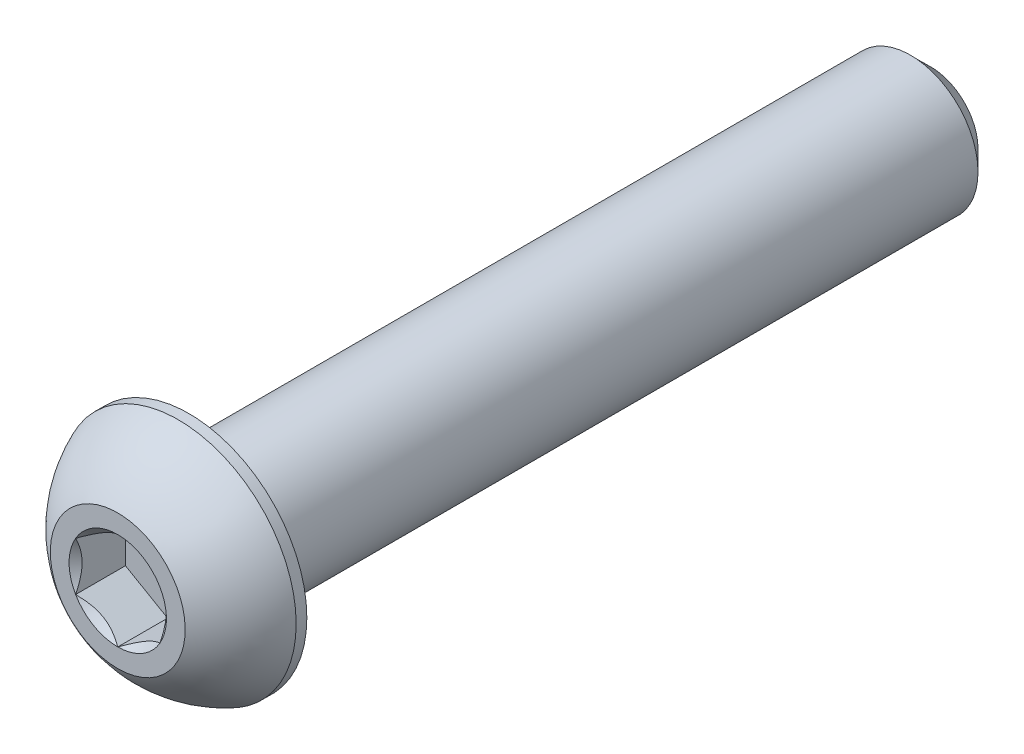
SolidWorks part; units mm, degrees
ref_plane "Front" through (0, 0, 0) normal (0, 0, 1) x (1, 0, 0)
ref_plane "Top" through (0, 0, 0) normal (0, 1, 0) x (1, 0, 0)
ref_plane "Right" through (0, 0, 0) normal (1, 0, 0) x (0, 0, -1)
sketch "Sketch1" plane through (0, 0, 0) normal (1, 0, 0) x (0, 0, -1)
  line L2 (3.3528, 3.175) -> (38.2778, 3.175)
  line L3 (38.2778, 3.175) -> (38.2778, 0)
  line L4 (38.2778, 0) -> (3.3528, 0)
  line L6 (2.8499, 5.5499) -> (3.3528, 5.5499) construction
  line L7 (38.2778, 3.175) -> (38.2778, -3.175) construction
  line L8 (0, 0) -> (3.3528, 0) construction
  line L9 (3.3528, 5.5499) -> (3.3528, -5.5499) construction
  line L11 (3.3528, 3.175) -> (3.3528, 0)
  line L13 (0, 1.9844) -> (0, -1.9844) construction
  line L14 (0, 1.9844) -> (0, 3.175) construction
  arc A3 (0, 3.175) -> (2.8499, 5.5499) centre (5.0603, 0) cw construction
  dimension "D1" = 0.5029
revolve "Revolve1" add sketch "Sketch1" angle 360 mid plane about L4
sketch "Sketch3" plane through (0, 0, -38.2778) normal (0, 0, -1) x (-1, 0, 0)
  circle A0 centre (0, 0) radius 3.175
curve "Helix/Spiral1" [suppressed] pitch 1.27 height 36.195 turns 28.5
sketch "Sketch2" plane through (0, 0, 0) normal (1, 0, 0) x (0, 0, -1)
  line L0 (38.2778, 3.175) -> (39.389, 3.175)
  line L1 (39.389, 3.175) -> (38.9128, 2.3501)
  line L2 (38.9128, 2.3501) -> (38.754, 2.3501)
  line L3 (38.754, 2.3501) -> (38.2778, 3.175)
  line L4 (38.5159, 2.7626) -> (39.1509, 2.7626) construction
  dimension "D1" = 60
  dimension "D2" = 0.1588
  dimension "D3" = 0.635
chamfer "Chamfer1" distance 0.9525 angle 45 1 edges at (0, 3.175, -38.2778)
sweep "Cut-Sweep1" [suppressed] cut profiles "Sketch2" path "Helix/Spiral1"
sketch "Sketch7" plane through (0, 0, 0) normal (1, 0, 0) x (0, 0, -1)
  line L6 (2.8499, 5.5499) -> (3.3528, 5.5499) construction
  line L8 (0, 0) -> (3.3528, 0) construction
  line L11 (3.3528, 5.5499) -> (3.3528, -5.5499) construction
  line L12 (2.8499, 5.5499) -> (3.3528, 5.5499)
  line L13 (0, 0) -> (3.3528, 0)
  line L14 (0, 1.9844) -> (0, -1.9844) construction
  line L15 (3.3528, 5.5499) -> (3.3528, 0)
  line L16 (0, 3.175) -> (0, 0)
  arc A2 (2.8499, 5.5499) -> (0, 3.175) centre (5.0603, 0) ccw construction
  arc A3 (2.8499, 5.5499) -> (0, 3.175) centre (5.0603, 0) ccw
revolve "Revolve2" add sketch "Sketch7" angle 360 mid plane about L13
sketch "Sketch5" plane through (0, 0, 0) normal (0, 0, 1) x (1, 0, 0)
  line L1 (1.9844, -1.1457) -> (1.9844, 1.1457)
  line L2 (1.9844, 1.1457) -> (0, 2.2914)
  line L3 (0, 2.2914) -> (-1.9844, 1.1457)
  line L4 (-1.9844, 1.1457) -> (-1.9844, -1.1457)
  line L5 (-1.9844, -1.1457) -> (0, -2.2914)
  line L6 (0, -2.2914) -> (1.9844, -1.1457)
  circle A0 centre (0, 0) radius 1.9844 construction
extrude "Cut-Extrude2" cut sketch "Sketch5" against normal blind 2.347
sketch "Sketch6" plane through (0, 0, 0) normal (0, 0, 1) x (1, 0, 0)
  circle A0 centre (0, 0) radius 2.2914
extrude "Cut-Extrude3" cut sketch "Sketch6" against normal blind 2.347 draft 45
sketch "Sketch9" [suppressed] plane through (0, 0, -3.3528) normal (0, 0, 1) x (1, 0, 0)
  circle A2 centre (0, 0) radius 3.175
extrude "Boss-Extrude2" [suppressed] add sketch "Sketch9" against normal offset from surface (25.4 mm away) 22.225
sketch "Sketch10" [suppressed] plane through (0, 0, 0) normal (1, 0, 0) x (0, 0, -1)
  line L0 (38.2778, 3.175) -> (38.2778, -3.175) construction
  point P0 (36.3728, -3.175)
  dimension "D1" = 1.905
equation "\"D3@Helix/Spiral1\" = \"Lg@Sketch1\" + \"D4@Helix/Spiral1\""
equation "\"D2@Sketch2\" = \"D4@Helix/Spiral1\" * .125"
equation "\"D3@Sketch2\" = \"D4@Helix/Spiral1\" * .5"
equation "\"D1@Chamfer1\" = \"D4@Helix/Spiral1\" * .75"
equation "\"D1@Cut-Extrude2\" = \"Head Ht@Sketch1\" * .7"
equation "\"D1@Sketch1\" = \"Head Ht@Sketch1\" * .15"
equation "\"D1@Sketch10\" = \"D4@Helix/Spiral1\" * 1.5"
equation "\"D1@Cut-Extrude3\" = \"D1@Cut-Extrude2\""
